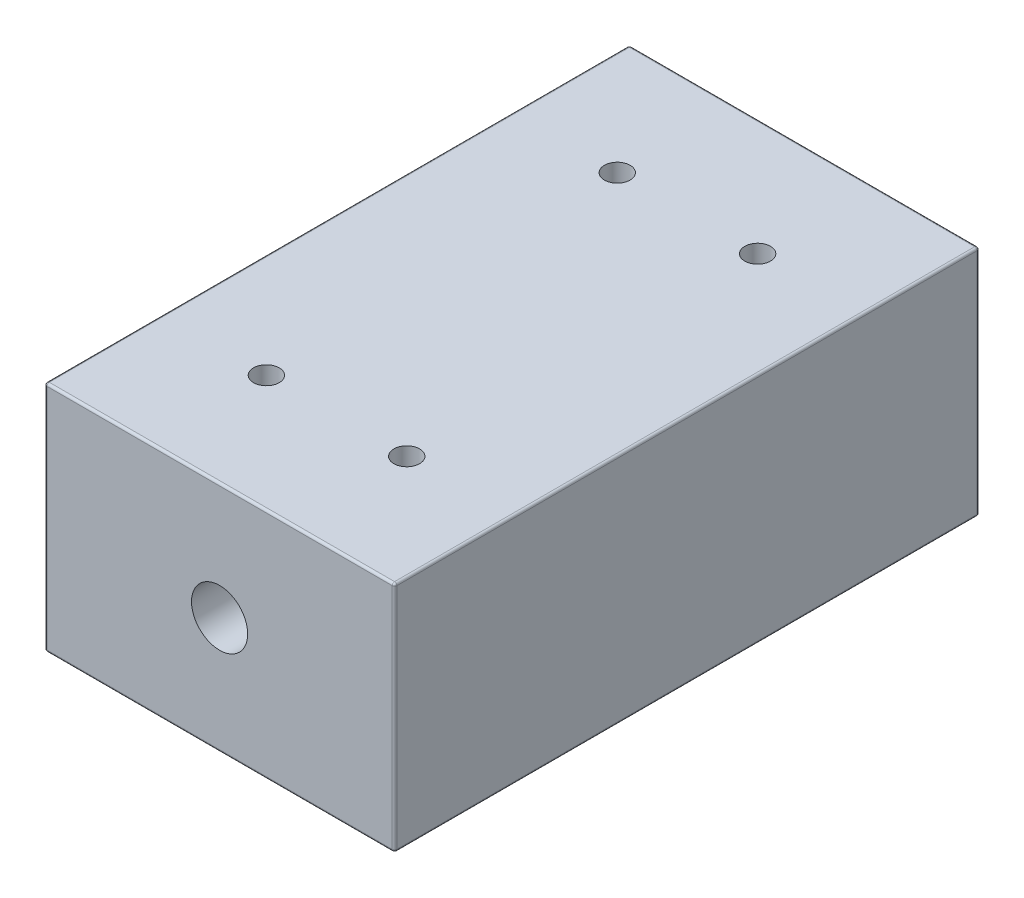
SolidWorks part; units mm, degrees
material "Beech"
ref_plane "Front Plane" through (0, 0, 0) normal (0, 0, 1) x (1, 0, 0)
ref_plane "Top Plane" through (0, 0, 0) normal (0, 1, 0) x (1, 0, 0)
ref_plane "Right Plane" through (0, 0, 0) normal (1, 0, 0) x (0, 0, -1)
sketch "Sketch1" plane through (0, 0, 0) normal (0, 0, 1) x (1, 0, 0)
  line L1 (0, 0) -> (74.8, 0)
  line L2 (0, 0) -> (0, 49.8)
  line L3 (0, 49.8) -> (74.8, 49.8)
  line L4 (74.8, 0) -> (74.8, 49.8)
  dimension "D1" = 74.8
  dimension "D2" = 49.8
extrude "slider body" add sketch "Sketch1" along normal blind 125
sketch "Sketch2" plane through (0, 0, 0) normal (0, 0, -1) x (-1, 0, 0)
  line L0 (-74.8, 49.8) -> (0, 0) construction
  line L1 (-74.8, 0) -> (0, 49.8) construction
  circle A0 centre (-37.4, 24.9) radius 11
  dimension "D1" = 22
extrude "lead nut inset" cut sketch "Sketch2" against normal blind 15
sketch "Sketch3" plane through (0, 0, 15) normal (0, 0, -1) x (-1, 0, 0)
  circle A0 centre (-37.4, 24.9) radius 6
  circle A1 centre (-37.4, 24.9) radius 11 construction
  dimension "D1" = 12
extrude "leadscrew clearance" cut sketch "Sketch3" against normal through all
fillet "corner break" radius 0.5 12 edges at (0, 24.9, 125) (0, 24.9, 0) (0, 0, 62.5) (37.4, 0, 125) (37.4, 0, 0) (74.8, 0, 62.5) (74.8, 24.9, 125) (74.8, 24.9, 0) (74.8, 49.8, 62.5) (37.4, 49.8, 125) (0, 49.8, 62.5) (37.4, 49.8, 0)
hole_wizard "bolt clearance holes" positions "Sketch4" profile "Sketch6" hole size "M5" standard "ANSI Metric" end condition through all
sketch "Sketch4" plane through (0, 49.8, 0) normal (0, 1, 0) x (1, 0, 0)
  line L1 (52.4, -100) -> (22.4, -100)
  line L2 (52.4, -100) -> (52.4, -25)
  line L3 (52.4, -25) -> (22.4, -25)
  line L4 (22.4, -100) -> (22.4, -25)
  line L5 (37.4, -100) -> (37.4, -124.5)
  line L6 (0.5, -124.5) -> (74.3, -124.5) construction
  line L8 (22.4, -62.5) -> (0.5, -62.5)
  line L9 (0.5, -0.5) -> (0.5, -124.5) construction
  point P1 (52.4, -100)
  point P2 (22.4, -25)
  point P47 (52.4, -25)
  point P48 (22.4, -100)
  dimension "D1" = 30
  dimension "D2" = 75
sketch "Sketch6" plane through (52.4, 49.8, 100) normal (1, 0, 0) x (0, 0, 1)
  line L0 (0, 0) -> (0, 49.8)
  line L1 (0, 49.8) -> (2.75, 49.8)
  line L2 (2.75, 49.8) -> (2.75, 0)
  line L5 (2.75, 0) -> (0, 0)
  line L11 (0, -6.35) -> (0, 107.95) construction
  dimension "Thru Hole Dia." = 5.5
  dimension "Thru Hole Depth" = 49.8
sketch "Sketch7" plane through (0, 0, 0) normal (0, -1, 0) x (1, 0, 0)
  circle A0 centre (22.4, 100) radius 6
  circle A1 centre (52.4, 100) radius 6
  circle A2 centre (52.4, 25) radius 6
  circle A3 centre (22.4, 25) radius 6
  dimension "D1" = 12
extrude "nut clearance counterbores" cut sketch "Sketch7" against normal blind 10
equation "\"board_thickness\" = 18mm"
equation "\"way_width\"= 75mm"
equation "\"way_thickness\"= 50mm"
equation "\"radial_clearance\"= 0.1mm"
equation "\"slider_width\"= \"way_width\"-2* \"radial_clearance\""
equation "\"slider_thickness\" = \"way_thickness\" - 2 * \"radial_clearance\""
equation "\"column_width\"= \"way_width\" + 2 * \"board_thickness\""
equation "\"boxway_slot_width\" = 50mm"
equation "\"keeper_rail_width\" = (\"column_width\" - \"boxway_slot_width\")/2"
equation "\"slider_length\" = 125mm"
equation "\"D1@Sketch1\"=\"slider_width\""
equation "\"D2@Sketch1\"=\"slider_thickness\""
equation "\"D1@slider body\" = \"slider_length\""
equation "\"nut_diameter\"= 22mm"
equation "\"nut_length\"= 15mm"
equation "\"D1@Sketch2\"=\"nut_diameter\""
equation "\"D1@lead nut inset\" = \"nut_length\""
equation "\"leadscrew_diameter\"= 10mm"
equation "\"leadscrew_radial_clearance\"= 1mm"
equation "\"D1@Sketch3\"=\"leadscrew_diameter\"+2* \"leadscrew_radial_clearance\""
equation "\"bearing_bolt_pattern_width\" = 30mm"
equation "\"bearing_bolt_pattern_height\" = 75mm"
equation "\"desktop_bolt_pattern_width\" = 30mm"
equation "\"desktop_bolt_pattern_height\" = 30mm"
equation "\"D1@Sketch4\"=\"bearing_bolt_pattern_width\""
equation "\"D2@Sketch4\"=\"bearing_bolt_pattern_height\""
equation "\"bearing_bolt_nut_counterbore_diameter\" = 12mm"
equation "\"bearing_bolt_nut_counterbore_depth\"= 10mm"
equation "\"D1@Sketch7\"=\"bearing_bolt_nut_counterbore_diameter\""
equation "\"D1@nut clearance counterbores\" = \"bearing_bolt_nut_counterbore_depth\""
